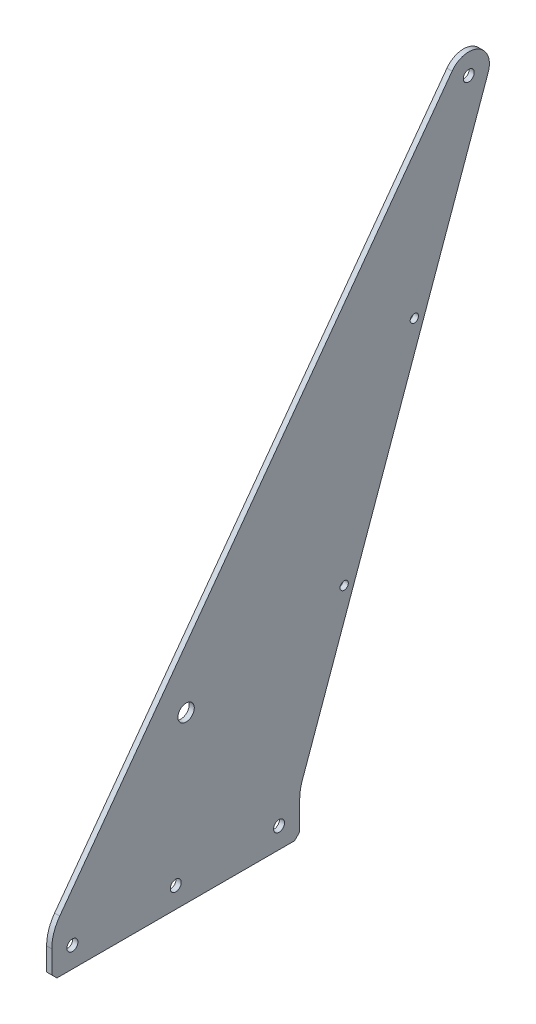
SolidWorks part; units mm, degrees
material "6061-T6 (SS)"
ref_plane "Front" through (0, 0, 0) normal (0, 0, 1) x (1, 0, 0)
ref_plane "Top" through (0, 0, 0) normal (0, 1, 0) x (1, 0, 0)
ref_plane "Right" through (0, 0, 0) normal (1, 0, 0) x (0, 0, -1)
sketch "Sketch1" plane through (0, 0, 0) normal (1, 0, 0) x (0, 0, -1)
  line L5 (82.55, 101.6) -> (-339.7504, 55.2196) construction
  line L6 (82.55, 101.6) -> (-0.4598, 518.2511) construction
  line L7 (256.271, 353.7228) -> (79.2701, 176.7219) construction
  line L8 (79.2701, 176.7219) -> (7.4281, 104.8799) construction
  line L9 (82.55, 101.6) -> (7.4281, 104.8799) construction
  line L10 (7.4281, 104.8799) -> (8.6793, 93.4869) construction
  line L11 (82.55, 101.6) -> (79.2701, 176.7219) construction
  line L12 (79.2701, 176.7219) -> (68.0296, 174.4825) construction
  circle A0 centre (82.55, 101.6) radius 5.0419
  dimension "D1" = 10.0838
  dimension "D3" = 82.55
  dimension "D2" = 101.6
  dimension "D4" = 45
  dimension "D7" = 46.3804
  dimension "D8" = 422.3004
  dimension "D9" = 85
  dimension "D10" = 101.6
  dimension "D11" = 250.317
sketch "Sketch2" plane through (0, 0, 0) normal (1, 0, 0) x (0, 0, -1)
  line L0 (0, 0) -> (0, 25.4)
  line L2 (0, 0) -> (152.4, 0)
  line L3 (152.4, 0) -> (152.4, 25.4)
  line L4 (152.4, 25.4) -> (268.2299, 349.4481)
  line L6 (0, 25.4) -> (246.026, 361.2282)
  arc A0 (268.2299, 349.4481) -> (246.026, 361.2282) centre (256.271, 353.7228) ccw
  circle A2 centre (82.55, 101.6) radius 5.0419 construction
  circle A3 centre (82.55, 101.6) radius 5.0419
  circle A4 centre (256.271, 353.7228) radius 3.3782
  dimension "D3" = 12.7
  dimension "D4" = 6.7564
  dimension "D1" = 25.4
  dimension "D2" = 152.4
extrude "Boss-Extrude2" add sketch "Sketch2" along normal blind 3.175
sketch "Sketch3" plane through (3.175, 0, 0) normal (1, 0, 0) x (0, 0, -1)
  line L0 (0, 0) -> (152.4, 0) construction
  line L1 (0, 25.4) -> (0, 0) construction
  line L2 (152.4, 0) -> (152.4, 25.4) construction
  line L3 (12.7, 12.7) -> (139.7, 12.7) construction
  line L4 (152.4, 25.4) -> (268.2299, 349.4481) construction
  line L5 (179.7024, 120.6474) -> (222.8274, 241.2948) construction
  line L6 (222.8274, 241.2948) -> (265.9524, 361.9422) construction
  line L7 (179.7024, 120.6474) -> (136.5774, 0) construction
  circle A0 centre (12.7, 12.7) radius 3.3782
  circle A1 centre (76.2, 12.7) radius 3.3782
  circle A2 centre (139.7, 12.7) radius 3.3782
  circle A3 centre (222.8274, 241.2948) radius 2.54
  circle A4 centre (179.7024, 120.6474) radius 2.54
  arc A5 (268.2299, 349.4481) -> (246.026, 361.2282) centre (256.271, 353.7228) ccw construction
  dimension "D1" = 12.7
  dimension "D2" = 12.7
  dimension "D3" = 12.7
  dimension "D4" = 6.7564
  dimension "D5" = 6.35
  dimension "D6" = 6.35
  dimension "D7" = 5.08
extrude "Cut-Extrude1" cut sketch "Sketch3" against normal through all
chamfer "Chamfer1" distance 3.175 angle 45 2 edges at (1.5875, 0, 0) (1.5875, 0, -152.4)
fillet "Fillet1" radius 25.4 2 edges at (1.5875, 25.4, -152.4) (1.5875, 25.4, 0)
